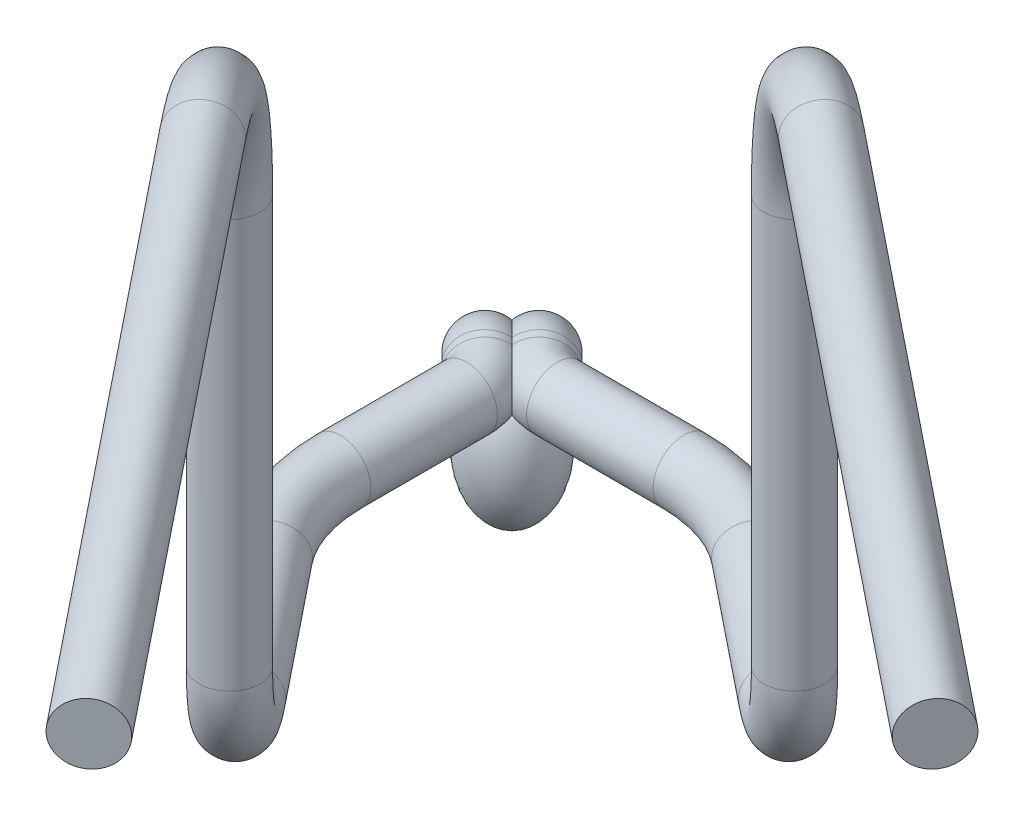
SolidWorks part; units mm, degrees
ref_plane "Front Plane" through (0, 0, 0) normal (0, 0, 1) x (1, 0, 0)
ref_plane "Top Plane" through (0, 0, 0) normal (0, 1, 0) x (1, 0, 0)
ref_plane "Right Plane" through (0, 0, 0) normal (1, 0, 0) x (0, 0, -1)
sketch "Sketch1" plane through (0, 0, 0) normal (0, 1, 0) x (1, 0, 0)
  line L0 (-2.1213, 2.1213) -> (0, 0) construction
  line L1 (0, 0) -> (0, 2.1213) construction
  line L2 (0, 2.1213) -> (-2.1213, 2.1213) construction
  circle A0 centre (0, 0) radius 1.5
  circle A1 centre (-2.1213, 2.1213) radius 0.75
  dimension "D1" = 1.5
  dimension "D2" = 3
  dimension "D3" = 3
  dimension "D4" = 45
ref_axis "Axis1" through (-2.1213, 0, -2.1213) along (0, 1, 0)
sketch3d "3DSketch1"
  line L0 (-1.6108, 0, -1.9214) -> (-1.5366, 0, -1.8473)
  line L1 (-1.1831, 0, -1.7008) -> (0.2677, 0, -1.7008)
  line L2 (1.5194, 0, -1.2607) -> (3.068, 0, -0.018)
  line L3 (-1.9643, -0.5, -2.275) -> (-1.9643, -0.6656, -2.275)
  line L4 (3.848, 1, 0.6079) -> (3.848, 5.6848, 0.6079)
  line L5 (-2.1213, 0, -2.1213) -> (0, 0, 0) construction
  line L6 (5.4078, 7.6848, 1.8596) -> (12.0096, 7.6848, 7.1574)
  arc A0 (-1.5366, 0, -1.8473) -> (-1.1831, 0, -1.7008) centre (-1.1831, 0, -2.2008) ccw
  arc A1 (-1.6108, 0, -1.9214) -> (-1.9643, -0.5, -2.275) centre (-1.6108, -0.5, -1.9214) ccw
  arc A2 (0.2677, 0, -1.7008) -> (1.5194, 0, -1.2607) centre (0.2677, 0, 0.2992) ccw
  arc A3 (3.068, 0, -0.018) -> (3.848, 1, 0.6079) centre (3.068, 1, -0.018) ccw
  arc A4 (3.848, 5.6848, 0.6079) -> (5.4078, 7.6848, 1.8596) centre (5.4078, 5.6848, 1.8596) ccw
  point P10 (3.848, 7.6848, 0.6079)
  point P12 (6.6596, 5.6848, 0.2998)
  point P15 (-1.3902, 0, -1.7008)
  point P16 (-1.1831, 0.5, -2.2008)
  point P20 (-1.9643, -0.5, -1.5679)
  point P23 (0.9709, 0, -1.7008)
  point P24 (0.2677, -2, 0.2992)
  point P29 (3.848, 0, 0.6079)
  point P30 (2.4422, 1, 0.7619)
  dimension "D1" = 0.5
  dimension "D2" = 2
  dimension "D3" = 1
  dimension "D4" = 2
ref_plane "Plane1" through (12.0096, 7.6848, 7.1574) normal (0.7799, 0, 0.6259) x (0.6259, 0, -0.7799)
sketch "Sketch2" plane through (12.0096, 7.6848, 7.1574) normal (0.7799, 0, 0.6259) x (0.6259, 0, -0.7799)
  circle A0 centre (0, 0) radius 0.35
  dimension "D1" = 0.7
sweep "Sweep1" add profiles "Sketch2" path "3DSketch1"
ref_plane "Plane2" through (0, 0, 0) normal (-0.7071, 0, 0.7071) x (0.7071, 0, 0.7071)
mirror "Mirror3" about plane through (0, 0, 0) normal (-0.7071, 0, 0.7071) of bodies 101
sketch "Sketch4" plane through (0, 0, 0) normal (-0.7071, 0, 0.7071) x (0.7071, 0, 0.7071)
  line L0 (-3, -0.4252) -> (-3, -1.9252)
  line L1 (-3, 0) -> (-3, 2.2441) construction
  ellipse E0 centre (-3, -1.1752) end of major axis (-3, -1.9252) minor radius 0.5 (-3, -0.4252) -> (-3, -1.9252) ccw
  dimension "D1" = 1.5
  dimension "D2" = 0.5
revolve "Revolve1" add sketch "Sketch4" angle 360 about L0
